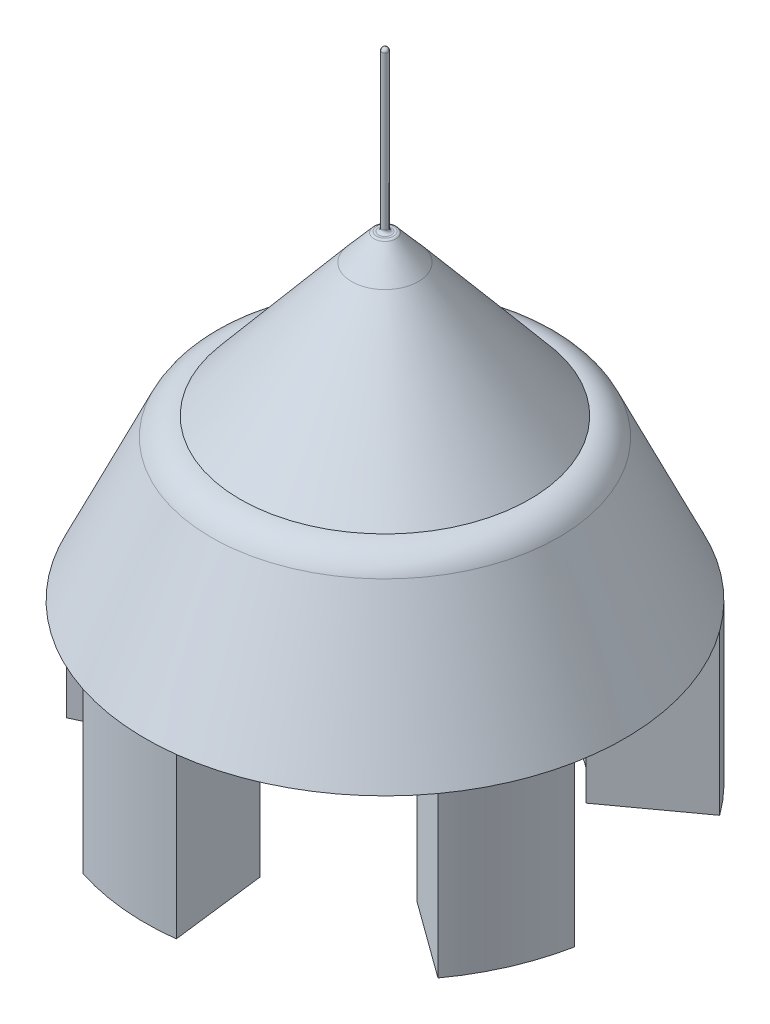
SolidWorks part; units mm, degrees
ref_plane "Plan de face" through (0, 0, 0) normal (0, 0, 1) x (1, 0, 0)
ref_plane "Plan de dessus" through (0, 0, 0) normal (0, 1, 0) x (1, 0, 0)
ref_plane "Plan de droite" through (0, 0, 0) normal (1, 0, 0) x (0, 0, -1)
sketch "profil Base" plane through (0, 0, 0) normal (0, 1, 0) x (1, 0, 0)
  circle A0 centre (0, 0) radius 75
  dimension "D1" = 150
extrude "Base" add sketch "profil Base" along normal blind 50 draft 25
fillet "Congé1" radius 10 1 edges at (0, 50, 51.6846)
sketch "Profil Pied" plane through (0, 0, 0) normal (0, -1, 0) x (1, 0, 0)
  line L0 (-75, 0) -> (-45, 0)
  line L1 (-67.9731, 31.6964) -> (-40.7839, 19.0178)
  arc A0 (-67.9731, 31.6964) -> (-75, 0) centre (0, 0) ccw
  arc A1 (-40.7839, 19.0178) -> (-45, 0) centre (0, 0) ccw
  circle A2 centre (0, 0) radius 75 construction
  point P1 (-26.3648, 20.8254)
  point P10 (-29.0697, 34.3504)
  dimension "D1" = 30
  dimension "D2" = 25
extrude "Pied" add sketch "Profil Pied" along normal blind 50
pattern_circular "Répétition circulaire1" count 5 over 360 about axis through (0, 0, 0) along (0, 1, 0) of "Pied"
sketch "Esquisse3" plane through (0, 50, 0) normal (0, 1, 0) x (1, 0, 0)
  circle A0 centre (0, 0) radius 45.3139
extrude "Boss.-Extru.3" add sketch "Esquisse3" along normal blind 50 draft 40
sketch "Esquisse5" plane through (0, 100, 0) normal (0, 1, 0) x (1, 0, 0)
  circle A0 centre (0, 0) radius 1
  dimension "D1" = 2
extrude "Boss.-Extru.4" add sketch "Esquisse5" along normal blind 50
fillet "Congé2" radius 1 1 edges at (0, 150, 1)
chamfer "Chanfrein1" distance 11 angle 1 1 edges at (0, 100, 3.3589) first distance on face at (0, 100, 3.3589)
fillet "Congé3" radius 1 1 edges at (0, 100, 3.1046)
fillet "Congé4" radius 1 1 edges at (0, 100, 1)
